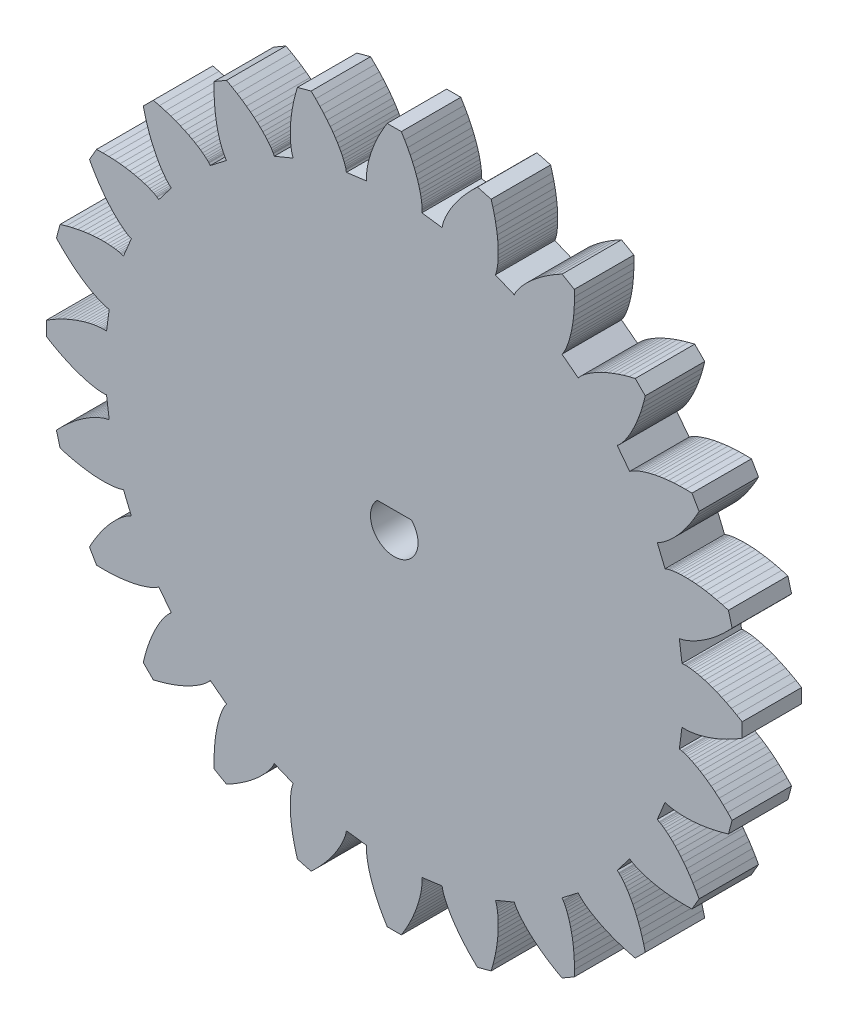
SolidWorks part; units mm, degrees
ref_plane "Front Plane" through (0, 0, 0) normal (0, 0, 1) x (1, 0, 0)
ref_plane "Top Plane" through (0, 0, 0) normal (0, 1, 0) x (1, 0, 0)
ref_plane "Right Plane" through (0, 0, 0) normal (1, 0, 0) x (0, 0, -1)
sketch "Model" plane through (0, 0, 0) normal (0, 0, 1) x (1, 0, 0)
  line L0 (24.1894, 2.3153) -> (24.359, 2.3315)
  line L1 (24.359, 2.3315) -> (24.3735, 2.3326)
  line L2 (24.3735, 2.3326) -> (24.417, 2.3344)
  line L3 (24.417, 2.3344) -> (24.4897, 2.335)
  line L4 (24.4897, 2.335) -> (24.5914, 2.3324)
  line L5 (24.5914, 2.3324) -> (24.7219, 2.3245)
  line L6 (24.7219, 2.3245) -> (24.8811, 2.3094)
  line L7 (24.8811, 2.3094) -> (25.0684, 2.2851)
  line L8 (25.0684, 2.2851) -> (25.2835, 2.2496)
  line L9 (25.2835, 2.2496) -> (25.5258, 2.201)
  line L10 (25.5258, 2.201) -> (25.7945, 2.1375)
  line L11 (25.7945, 2.1375) -> (26.0888, 2.057)
  line L12 (26.0888, 2.057) -> (26.4081, 1.9579)
  line L13 (26.4081, 1.9579) -> (26.7511, 1.8382)
  line L14 (26.7511, 1.8382) -> (27.1169, 1.6963)
  line L15 (27.1169, 1.6963) -> (27.5043, 1.5304)
  line L16 (27.5043, 1.5304) -> (27.9121, 1.339)
  line L17 (27.9121, 1.339) -> (28.339, 1.1203)
  line L18 (28.339, 1.1203) -> (28.7834, 0.8729)
  line L19 (28.7834, 0.8729) -> (29.244, 0.5954)
  line L20 (29.244, 0.5954) -> (29.244, -0.5954)
  line L21 (29.244, -0.5954) -> (28.7834, -0.8729)
  line L22 (28.7834, -0.8729) -> (28.339, -1.1203)
  line L23 (28.339, -1.1203) -> (27.9121, -1.339)
  line L24 (27.9121, -1.339) -> (27.5043, -1.5304)
  line L25 (27.5043, -1.5304) -> (27.1169, -1.6963)
  line L26 (27.1169, -1.6963) -> (26.7511, -1.8382)
  line L27 (26.7511, -1.8382) -> (26.4081, -1.9579)
  line L28 (26.4081, -1.9579) -> (26.0888, -2.057)
  line L29 (26.0888, -2.057) -> (25.7945, -2.1375)
  line L30 (25.7945, -2.1375) -> (25.5258, -2.201)
  line L31 (25.5258, -2.201) -> (25.2835, -2.2496)
  line L32 (25.2835, -2.2496) -> (25.0684, -2.2851)
  line L33 (25.0684, -2.2851) -> (24.8811, -2.3094)
  line L34 (24.8811, -2.3094) -> (24.7219, -2.3245)
  line L35 (24.7219, -2.3245) -> (24.5914, -2.3324)
  line L36 (24.5914, -2.3324) -> (24.4897, -2.335)
  line L37 (24.4897, -2.335) -> (24.417, -2.3344)
  line L38 (24.417, -2.3344) -> (24.3735, -2.3326)
  line L39 (24.3735, -2.3326) -> (24.359, -2.3315)
  line L40 (24.359, -2.3315) -> (24.1894, -2.3153)
  line L41 (24.1894, -2.3153) -> (23.9645, -4.0243)
  line L42 (23.9645, -4.0243) -> (24.1324, -4.0525)
  line L43 (24.1324, -4.0525) -> (24.1467, -4.0552)
  line L44 (24.1467, -4.0552) -> (24.1892, -4.0647)
  line L45 (24.1892, -4.0647) -> (24.2596, -4.083)
  line L46 (24.2596, -4.083) -> (24.3571, -4.1118)
  line L47 (24.3571, -4.1118) -> (24.4812, -4.1532)
  line L48 (24.4812, -4.1532) -> (24.631, -4.209)
  line L49 (24.631, -4.209) -> (24.8057, -4.281)
  line L50 (24.8057, -4.281) -> (25.0042, -4.3709)
  line L51 (25.0042, -4.3709) -> (25.2257, -4.4805)
  line L52 (25.2257, -4.4805) -> (25.4687, -4.6115)
  line L53 (25.4687, -4.6115) -> (25.7323, -4.7654)
  line L54 (25.7323, -4.7654) -> (26.015, -4.9437)
  line L55 (26.015, -4.9437) -> (26.3153, -5.1481)
  line L56 (26.3153, -5.1481) -> (26.632, -5.3799)
  line L57 (26.632, -5.3799) -> (26.9633, -5.6404)
  line L58 (26.9633, -5.6404) -> (27.3076, -5.9309)
  line L59 (27.3076, -5.9309) -> (27.6633, -6.2525)
  line L60 (27.6633, -6.2525) -> (28.0286, -6.6065)
  line L61 (28.0286, -6.6065) -> (28.4016, -6.9938)
  line L62 (28.4016, -6.9938) -> (28.0934, -8.144)
  line L63 (28.0934, -8.144) -> (27.5767, -8.2929)
  line L64 (27.5767, -8.2929) -> (27.0834, -8.4168)
  line L65 (27.0834, -8.4168) -> (26.6145, -8.5175)
  line L66 (26.6145, -8.5175) -> (26.1711, -8.5969)
  line L67 (26.1711, -8.5969) -> (25.7539, -8.6569)
  line L68 (25.7539, -8.6569) -> (25.3638, -8.6993)
  line L69 (25.3638, -8.6993) -> (25.0015, -8.7261)
  line L70 (25.0015, -8.7261) -> (24.6675, -8.7392)
  line L71 (24.6675, -8.7392) -> (24.3623, -8.7407)
  line L72 (24.3623, -8.7407) -> (24.0863, -8.7326)
  line L73 (24.0863, -8.7326) -> (23.8398, -8.7168)
  line L74 (23.8398, -8.7168) -> (23.6228, -8.6954)
  line L75 (23.6228, -8.6954) -> (23.4356, -8.6704)
  line L76 (23.4356, -8.6704) -> (23.2779, -8.6438)
  line L77 (23.2779, -8.6438) -> (23.1498, -8.6176)
  line L78 (23.1498, -8.6176) -> (23.0509, -8.5938)
  line L79 (23.0509, -8.5938) -> (22.9809, -8.5745)
  line L80 (22.9809, -8.5745) -> (22.9392, -8.5614)
  line L81 (22.9392, -8.5614) -> (22.9255, -8.5567)
  line L82 (22.9255, -8.5567) -> (22.766, -8.4971)
  line L83 (22.766, -8.4971) -> (22.1063, -10.0896)
  line L84 (22.1063, -10.0896) -> (22.2613, -10.1603)
  line L85 (22.2613, -10.1603) -> (22.2743, -10.1666)
  line L86 (22.2743, -10.1666) -> (22.313, -10.1868)
  line L87 (22.313, -10.1868) -> (22.3762, -10.2227)
  line L88 (22.3762, -10.2227) -> (22.463, -10.2758)
  line L89 (22.463, -10.2758) -> (22.5721, -10.3479)
  line L90 (22.5721, -10.3479) -> (22.7023, -10.4406)
  line L91 (22.7023, -10.4406) -> (22.8524, -10.5553)
  line L92 (22.8524, -10.5553) -> (23.021, -10.6936)
  line L93 (23.021, -10.6936) -> (23.2065, -10.8567)
  line L94 (23.2065, -10.8567) -> (23.4074, -11.0461)
  line L95 (23.4074, -11.0461) -> (23.6221, -11.263)
  line L96 (23.6221, -11.263) -> (23.849, -11.5085)
  line L97 (23.849, -11.5085) -> (24.0862, -11.7836)
  line L98 (24.0862, -11.7836) -> (24.3321, -12.0894)
  line L99 (24.3321, -12.0894) -> (24.5847, -12.4268)
  line L100 (24.5847, -12.4268) -> (24.8421, -12.7965)
  line L101 (24.8421, -12.7965) -> (25.1024, -13.1993)
  line L102 (25.1024, -13.1993) -> (25.3636, -13.6357)
  line L103 (25.3636, -13.6357) -> (25.6237, -14.1063)
  line L104 (25.6237, -14.1063) -> (25.0283, -15.1376)
  line L105 (25.0283, -15.1376) -> (24.4907, -15.1477)
  line L106 (24.4907, -15.1477) -> (23.9821, -15.1397)
  line L107 (23.9821, -15.1397) -> (23.5031, -15.1156)
  line L108 (23.5031, -15.1156) -> (23.0542, -15.0776)
  line L109 (23.0542, -15.0776) -> (22.6358, -15.0275)
  line L110 (22.6358, -15.0275) -> (22.248, -14.9675)
  line L111 (22.248, -14.9675) -> (21.8911, -14.8996)
  line L112 (21.8911, -14.8996) -> (21.5651, -14.8259)
  line L113 (21.5651, -14.8259) -> (21.2699, -14.7483)
  line L114 (21.2699, -14.7483) -> (21.0054, -14.669)
  line L115 (21.0054, -14.669) -> (20.7714, -14.59)
  line L116 (20.7714, -14.59) -> (20.5674, -14.5131)
  line L117 (20.5674, -14.5131) -> (20.393, -14.4405)
  line L118 (20.393, -14.4405) -> (20.2476, -14.374)
  line L119 (20.2476, -14.374) -> (20.1306, -14.3156)
  line L120 (20.1306, -14.3156) -> (20.0412, -14.267)
  line L121 (20.0412, -14.267) -> (19.9786, -14.2302)
  line L122 (19.9786, -14.2302) -> (19.9417, -14.2068)
  line L123 (19.9417, -14.2068) -> (19.9297, -14.1987)
  line L124 (19.9297, -14.1987) -> (19.791, -14.0998)
  line L125 (19.791, -14.0998) -> (18.7417, -15.4673)
  line L126 (18.7417, -15.4673) -> (18.8731, -15.5757)
  line L127 (18.8731, -15.5757) -> (18.884, -15.5853)
  line L128 (18.884, -15.5853) -> (18.9161, -15.6148)
  line L129 (18.9161, -15.6148) -> (18.9679, -15.6657)
  line L130 (18.9679, -15.6657) -> (19.038, -15.7395)
  line L131 (19.038, -15.7395) -> (19.1247, -15.8374)
  line L132 (19.1247, -15.8374) -> (19.2266, -15.9606)
  line L133 (19.2266, -15.9606) -> (19.3418, -16.1103)
  line L134 (19.3418, -16.1103) -> (19.4689, -16.2874)
  line L135 (19.4689, -16.2874) -> (19.6058, -16.4931)
  line L136 (19.6058, -16.4931) -> (19.7509, -16.728)
  line L137 (19.7509, -16.728) -> (19.9021, -16.9931)
  line L138 (19.9021, -16.9931) -> (20.0577, -17.2889)
  line L139 (20.0577, -17.2889) -> (20.2157, -17.6161)
  line L140 (20.2157, -17.6161) -> (20.374, -17.9751)
  line L141 (20.374, -17.9751) -> (20.5307, -18.3663)
  line L142 (20.5307, -18.3663) -> (20.6837, -18.7901)
  line L143 (20.6837, -18.7901) -> (20.8309, -19.2465)
  line L144 (20.8309, -19.2465) -> (20.9702, -19.7357)
  line L145 (20.9702, -19.7357) -> (21.0996, -20.2576)
  line L146 (21.0996, -20.2576) -> (20.2576, -21.0996)
  line L147 (20.2576, -21.0996) -> (19.7357, -20.9702)
  line L148 (19.7357, -20.9702) -> (19.2465, -20.8309)
  line L149 (19.2465, -20.8309) -> (18.7901, -20.6837)
  line L150 (18.7901, -20.6837) -> (18.3663, -20.5307)
  line L151 (18.3663, -20.5307) -> (17.9751, -20.374)
  line L152 (17.9751, -20.374) -> (17.6161, -20.2157)
  line L153 (17.6161, -20.2157) -> (17.2889, -20.0577)
  line L154 (17.2889, -20.0577) -> (16.9931, -19.9021)
  line L155 (16.9931, -19.9021) -> (16.728, -19.7509)
  line L156 (16.728, -19.7509) -> (16.4931, -19.6058)
  line L157 (16.4931, -19.6058) -> (16.2874, -19.4689)
  line L158 (16.2874, -19.4689) -> (16.1103, -19.3418)
  line L159 (16.1103, -19.3418) -> (15.9606, -19.2266)
  line L160 (15.9606, -19.2266) -> (15.8374, -19.1247)
  line L161 (15.8374, -19.1247) -> (15.7395, -19.038)
  line L162 (15.7395, -19.038) -> (15.6657, -18.9679)
  line L163 (15.6657, -18.9679) -> (15.6148, -18.9161)
  line L164 (15.6148, -18.9161) -> (15.5853, -18.884)
  line L165 (15.5853, -18.884) -> (15.5757, -18.8731)
  line L166 (15.5757, -18.8731) -> (15.4673, -18.7417)
  line L167 (15.4673, -18.7417) -> (14.0998, -19.791)
  line L168 (14.0998, -19.791) -> (14.1987, -19.9297)
  line L169 (14.1987, -19.9297) -> (14.2068, -19.9417)
  line L170 (14.2068, -19.9417) -> (14.2302, -19.9786)
  line L171 (14.2302, -19.9786) -> (14.267, -20.0412)
  line L172 (14.267, -20.0412) -> (14.3156, -20.1306)
  line L173 (14.3156, -20.1306) -> (14.374, -20.2476)
  line L174 (14.374, -20.2476) -> (14.4405, -20.393)
  line L175 (14.4405, -20.393) -> (14.5131, -20.5674)
  line L176 (14.5131, -20.5674) -> (14.59, -20.7714)
  line L177 (14.59, -20.7714) -> (14.669, -21.0054)
  line L178 (14.669, -21.0054) -> (14.7483, -21.2699)
  line L179 (14.7483, -21.2699) -> (14.8259, -21.5651)
  line L180 (14.8259, -21.5651) -> (14.8996, -21.8911)
  line L181 (14.8996, -21.8911) -> (14.9675, -22.248)
  line L182 (14.9675, -22.248) -> (15.0275, -22.6358)
  line L183 (15.0275, -22.6358) -> (15.0776, -23.0542)
  line L184 (15.0776, -23.0542) -> (15.1156, -23.5031)
  line L185 (15.1156, -23.5031) -> (15.1397, -23.9821)
  line L186 (15.1397, -23.9821) -> (15.1477, -24.4907)
  line L187 (15.1477, -24.4907) -> (15.1376, -25.0283)
  line L188 (15.1376, -25.0283) -> (14.1063, -25.6237)
  line L189 (14.1063, -25.6237) -> (13.6357, -25.3636)
  line L190 (13.6357, -25.3636) -> (13.1993, -25.1024)
  line L191 (13.1993, -25.1024) -> (12.7965, -24.8421)
  line L192 (12.7965, -24.8421) -> (12.4268, -24.5847)
  line L193 (12.4268, -24.5847) -> (12.0894, -24.3321)
  line L194 (12.0894, -24.3321) -> (11.7836, -24.0862)
  line L195 (11.7836, -24.0862) -> (11.5085, -23.849)
  line L196 (11.5085, -23.849) -> (11.263, -23.6221)
  line L197 (11.263, -23.6221) -> (11.0461, -23.4074)
  line L198 (11.0461, -23.4074) -> (10.8567, -23.2065)
  line L199 (10.8567, -23.2065) -> (10.6936, -23.021)
  line L200 (10.6936, -23.021) -> (10.5553, -22.8524)
  line L201 (10.5553, -22.8524) -> (10.4406, -22.7023)
  line L202 (10.4406, -22.7023) -> (10.3479, -22.5721)
  line L203 (10.3479, -22.5721) -> (10.2758, -22.463)
  line L204 (10.2758, -22.463) -> (10.2227, -22.3762)
  line L205 (10.2227, -22.3762) -> (10.1868, -22.313)
  line L206 (10.1868, -22.313) -> (10.1666, -22.2743)
  line L207 (10.1666, -22.2743) -> (10.1603, -22.2613)
  line L208 (10.1603, -22.2613) -> (10.0896, -22.1063)
  line L209 (10.0896, -22.1063) -> (8.4971, -22.766)
  line L210 (8.4971, -22.766) -> (8.5567, -22.9255)
  line L211 (8.5567, -22.9255) -> (8.5614, -22.9392)
  line L212 (8.5614, -22.9392) -> (8.5745, -22.9809)
  line L213 (8.5745, -22.9809) -> (8.5938, -23.0509)
  line L214 (8.5938, -23.0509) -> (8.6176, -23.1498)
  line L215 (8.6176, -23.1498) -> (8.6438, -23.2779)
  line L216 (8.6438, -23.2779) -> (8.6704, -23.4356)
  line L217 (8.6704, -23.4356) -> (8.6954, -23.6228)
  line L218 (8.6954, -23.6228) -> (8.7168, -23.8398)
  line L219 (8.7168, -23.8398) -> (8.7326, -24.0863)
  line L220 (8.7326, -24.0863) -> (8.7407, -24.3623)
  line L221 (8.7407, -24.3623) -> (8.7392, -24.6675)
  line L222 (8.7392, -24.6675) -> (8.7261, -25.0015)
  line L223 (8.7261, -25.0015) -> (8.6993, -25.3638)
  line L224 (8.6993, -25.3638) -> (8.6569, -25.7539)
  line L225 (8.6569, -25.7539) -> (8.5969, -26.1711)
  line L226 (8.5969, -26.1711) -> (8.5175, -26.6145)
  line L227 (8.5175, -26.6145) -> (8.4168, -27.0834)
  line L228 (8.4168, -27.0834) -> (8.2929, -27.5767)
  line L229 (8.2929, -27.5767) -> (8.144, -28.0934)
  line L230 (8.144, -28.0934) -> (6.9938, -28.4016)
  line L231 (6.9938, -28.4016) -> (6.6065, -28.0286)
  line L232 (6.6065, -28.0286) -> (6.2525, -27.6633)
  line L233 (6.2525, -27.6633) -> (5.9309, -27.3076)
  line L234 (5.9309, -27.3076) -> (5.6404, -26.9633)
  line L235 (5.6404, -26.9633) -> (5.3799, -26.632)
  line L236 (5.3799, -26.632) -> (5.1481, -26.3153)
  line L237 (5.1481, -26.3153) -> (4.9437, -26.015)
  line L238 (4.9437, -26.015) -> (4.7654, -25.7323)
  line L239 (4.7654, -25.7323) -> (4.6115, -25.4687)
  line L240 (4.6115, -25.4687) -> (4.4805, -25.2257)
  line L241 (4.4805, -25.2257) -> (4.3709, -25.0042)
  line L242 (4.3709, -25.0042) -> (4.281, -24.8057)
  line L243 (4.281, -24.8057) -> (4.209, -24.631)
  line L244 (4.209, -24.631) -> (4.1532, -24.4812)
  line L245 (4.1532, -24.4812) -> (4.1118, -24.3571)
  line L246 (4.1118, -24.3571) -> (4.083, -24.2596)
  line L247 (4.083, -24.2596) -> (4.0647, -24.1892)
  line L248 (4.0647, -24.1892) -> (4.0552, -24.1467)
  line L249 (4.0552, -24.1467) -> (4.0525, -24.1324)
  line L250 (4.0525, -24.1324) -> (4.0243, -23.9645)
  line L251 (4.0243, -23.9645) -> (2.3153, -24.1894)
  line L252 (2.3153, -24.1894) -> (2.3315, -24.359)
  line L253 (2.3315, -24.359) -> (2.3326, -24.3735)
  line L254 (2.3326, -24.3735) -> (2.3344, -24.417)
  line L255 (2.3344, -24.417) -> (2.335, -24.4897)
  line L256 (2.335, -24.4897) -> (2.3324, -24.5914)
  line L257 (2.3324, -24.5914) -> (2.3245, -24.7219)
  line L258 (2.3245, -24.7219) -> (2.3094, -24.8811)
  line L259 (2.3094, -24.8811) -> (2.2851, -25.0684)
  line L260 (2.2851, -25.0684) -> (2.2496, -25.2835)
  line L261 (2.2496, -25.2835) -> (2.201, -25.5258)
  line L262 (2.201, -25.5258) -> (2.1375, -25.7945)
  line L263 (2.1375, -25.7945) -> (2.057, -26.0888)
  line L264 (2.057, -26.0888) -> (1.9579, -26.4081)
  line L265 (1.9579, -26.4081) -> (1.8382, -26.7511)
  line L266 (1.8382, -26.7511) -> (1.6963, -27.1169)
  line L267 (1.6963, -27.1169) -> (1.5304, -27.5043)
  line L268 (1.5304, -27.5043) -> (1.339, -27.9121)
  line L269 (1.339, -27.9121) -> (1.1203, -28.339)
  line L270 (1.1203, -28.339) -> (0.8729, -28.7834)
  line L271 (0.8729, -28.7834) -> (0.5954, -29.244)
  line L272 (0.5954, -29.244) -> (-0.5954, -29.244)
  line L273 (-0.5954, -29.244) -> (-0.8729, -28.7834)
  line L274 (-0.8729, -28.7834) -> (-1.1203, -28.339)
  line L275 (-1.1203, -28.339) -> (-1.339, -27.9121)
  line L276 (-1.339, -27.9121) -> (-1.5304, -27.5043)
  line L277 (-1.5304, -27.5043) -> (-1.6963, -27.1169)
  line L278 (-1.6963, -27.1169) -> (-1.8382, -26.7511)
  line L279 (-1.8382, -26.7511) -> (-1.9579, -26.4081)
  line L280 (-1.9579, -26.4081) -> (-2.057, -26.0888)
  line L281 (-2.057, -26.0888) -> (-2.1375, -25.7945)
  line L282 (-2.1375, -25.7945) -> (-2.201, -25.5258)
  line L283 (-2.201, -25.5258) -> (-2.2496, -25.2835)
  line L284 (-2.2496, -25.2835) -> (-2.2851, -25.0684)
  line L285 (-2.2851, -25.0684) -> (-2.3094, -24.8811)
  line L286 (-2.3094, -24.8811) -> (-2.3245, -24.7219)
  line L287 (-2.3245, -24.7219) -> (-2.3324, -24.5914)
  line L288 (-2.3324, -24.5914) -> (-2.335, -24.4897)
  line L289 (-2.335, -24.4897) -> (-2.3344, -24.417)
  line L290 (-2.3344, -24.417) -> (-2.3326, -24.3735)
  line L291 (-2.3326, -24.3735) -> (-2.3315, -24.359)
  line L292 (-2.3315, -24.359) -> (-2.3153, -24.1894)
  line L293 (-2.3153, -24.1894) -> (-4.0243, -23.9645)
  line L294 (-4.0243, -23.9645) -> (-4.0525, -24.1324)
  line L295 (-4.0525, -24.1324) -> (-4.0552, -24.1467)
  line L296 (-4.0552, -24.1467) -> (-4.0647, -24.1892)
  line L297 (-4.0647, -24.1892) -> (-4.083, -24.2596)
  line L298 (-4.083, -24.2596) -> (-4.1118, -24.3571)
  line L299 (-4.1118, -24.3571) -> (-4.1532, -24.4812)
  line L300 (-4.1532, -24.4812) -> (-4.209, -24.631)
  line L301 (-4.209, -24.631) -> (-4.281, -24.8057)
  line L302 (-4.281, -24.8057) -> (-4.3709, -25.0042)
  line L303 (-4.3709, -25.0042) -> (-4.4805, -25.2257)
  line L304 (-4.4805, -25.2257) -> (-4.6115, -25.4687)
  line L305 (-4.6115, -25.4687) -> (-4.7654, -25.7323)
  line L306 (-4.7654, -25.7323) -> (-4.9437, -26.015)
  line L307 (-4.9437, -26.015) -> (-5.1481, -26.3153)
  line L308 (-5.1481, -26.3153) -> (-5.3799, -26.632)
  line L309 (-5.3799, -26.632) -> (-5.6404, -26.9633)
  line L310 (-5.6404, -26.9633) -> (-5.9309, -27.3076)
  line L311 (-5.9309, -27.3076) -> (-6.2525, -27.6633)
  line L312 (-6.2525, -27.6633) -> (-6.6065, -28.0286)
  line L313 (-6.6065, -28.0286) -> (-6.9938, -28.4016)
  line L314 (-6.9938, -28.4016) -> (-8.144, -28.0934)
  line L315 (-8.144, -28.0934) -> (-8.2929, -27.5767)
  line L316 (-8.2929, -27.5767) -> (-8.4168, -27.0834)
  line L317 (-8.4168, -27.0834) -> (-8.5175, -26.6145)
  line L318 (-8.5175, -26.6145) -> (-8.5969, -26.1711)
  line L319 (-8.5969, -26.1711) -> (-8.6569, -25.7539)
  line L320 (-8.6569, -25.7539) -> (-8.6993, -25.3638)
  line L321 (-8.6993, -25.3638) -> (-8.7261, -25.0015)
  line L322 (-8.7261, -25.0015) -> (-8.7392, -24.6675)
  line L323 (-8.7392, -24.6675) -> (-8.7407, -24.3623)
  line L324 (-8.7407, -24.3623) -> (-8.7326, -24.0863)
  line L325 (-8.7326, -24.0863) -> (-8.7168, -23.8398)
  line L326 (-8.7168, -23.8398) -> (-8.6954, -23.6228)
  line L327 (-8.6954, -23.6228) -> (-8.6704, -23.4356)
  line L328 (-8.6704, -23.4356) -> (-8.6438, -23.2779)
  line L329 (-8.6438, -23.2779) -> (-8.6176, -23.1498)
  line L330 (-8.6176, -23.1498) -> (-8.5938, -23.0509)
  line L331 (-8.5938, -23.0509) -> (-8.5745, -22.9809)
  line L332 (-8.5745, -22.9809) -> (-8.5614, -22.9392)
  line L333 (-8.5614, -22.9392) -> (-8.5567, -22.9255)
  line L334 (-8.5567, -22.9255) -> (-8.4971, -22.766)
  line L335 (-8.4971, -22.766) -> (-10.0896, -22.1063)
  line L336 (-10.0896, -22.1063) -> (-10.1603, -22.2613)
  line L337 (-10.1603, -22.2613) -> (-10.1666, -22.2743)
  line L338 (-10.1666, -22.2743) -> (-10.1868, -22.313)
  line L339 (-10.1868, -22.313) -> (-10.2227, -22.3762)
  line L340 (-10.2227, -22.3762) -> (-10.2758, -22.463)
  line L341 (-10.2758, -22.463) -> (-10.3479, -22.5721)
  line L342 (-10.3479, -22.5721) -> (-10.4406, -22.7023)
  line L343 (-10.4406, -22.7023) -> (-10.5553, -22.8524)
  line L344 (-10.5553, -22.8524) -> (-10.6936, -23.021)
  line L345 (-10.6936, -23.021) -> (-10.8567, -23.2065)
  line L346 (-10.8567, -23.2065) -> (-11.0461, -23.4074)
  line L347 (-11.0461, -23.4074) -> (-11.263, -23.6221)
  line L348 (-11.263, -23.6221) -> (-11.5085, -23.849)
  line L349 (-11.5085, -23.849) -> (-11.7836, -24.0862)
  line L350 (-11.7836, -24.0862) -> (-12.0894, -24.3321)
  line L351 (-12.0894, -24.3321) -> (-12.4268, -24.5847)
  line L352 (-12.4268, -24.5847) -> (-12.7965, -24.8421)
  line L353 (-12.7965, -24.8421) -> (-13.1993, -25.1024)
  line L354 (-13.1993, -25.1024) -> (-13.6357, -25.3636)
  line L355 (-13.6357, -25.3636) -> (-14.1063, -25.6237)
  line L356 (-14.1063, -25.6237) -> (-15.1376, -25.0283)
  line L357 (-15.1376, -25.0283) -> (-15.1477, -24.4907)
  line L358 (-15.1477, -24.4907) -> (-15.1397, -23.9821)
  line L359 (-15.1397, -23.9821) -> (-15.1156, -23.5031)
  line L360 (-15.1156, -23.5031) -> (-15.0776, -23.0542)
  line L361 (-15.0776, -23.0542) -> (-15.0275, -22.6358)
  line L362 (-15.0275, -22.6358) -> (-14.9675, -22.248)
  line L363 (-14.9675, -22.248) -> (-14.8996, -21.8911)
  line L364 (-14.8996, -21.8911) -> (-14.8259, -21.5651)
  line L365 (-14.8259, -21.5651) -> (-14.7483, -21.2699)
  line L366 (-14.7483, -21.2699) -> (-14.669, -21.0054)
  line L367 (-14.669, -21.0054) -> (-14.59, -20.7714)
  line L368 (-14.59, -20.7714) -> (-14.5131, -20.5674)
  line L369 (-14.5131, -20.5674) -> (-14.4405, -20.393)
  line L370 (-14.4405, -20.393) -> (-14.374, -20.2476)
  line L371 (-14.374, -20.2476) -> (-14.3156, -20.1306)
  line L372 (-14.3156, -20.1306) -> (-14.267, -20.0412)
  line L373 (-14.267, -20.0412) -> (-14.2302, -19.9786)
  line L374 (-14.2302, -19.9786) -> (-14.2068, -19.9417)
  line L375 (-14.2068, -19.9417) -> (-14.1987, -19.9297)
  line L376 (-14.1987, -19.9297) -> (-14.0998, -19.791)
  line L377 (-14.0998, -19.791) -> (-15.4673, -18.7417)
  line L378 (-15.4673, -18.7417) -> (-15.5757, -18.8731)
  line L379 (-15.5757, -18.8731) -> (-15.5853, -18.884)
  line L380 (-15.5853, -18.884) -> (-15.6148, -18.9161)
  line L381 (-15.6148, -18.9161) -> (-15.6657, -18.9679)
  line L382 (-15.6657, -18.9679) -> (-15.7395, -19.038)
  line L383 (-15.7395, -19.038) -> (-15.8374, -19.1247)
  line L384 (-15.8374, -19.1247) -> (-15.9606, -19.2266)
  line L385 (-15.9606, -19.2266) -> (-16.1103, -19.3418)
  line L386 (-16.1103, -19.3418) -> (-16.2874, -19.4689)
  line L387 (-16.2874, -19.4689) -> (-16.4931, -19.6058)
  line L388 (-16.4931, -19.6058) -> (-16.728, -19.7509)
  line L389 (-16.728, -19.7509) -> (-16.9931, -19.9021)
  line L390 (-16.9931, -19.9021) -> (-17.2889, -20.0577)
  line L391 (-17.2889, -20.0577) -> (-17.6161, -20.2157)
  line L392 (-17.6161, -20.2157) -> (-17.9751, -20.374)
  line L393 (-17.9751, -20.374) -> (-18.3663, -20.5307)
  line L394 (-18.3663, -20.5307) -> (-18.7901, -20.6837)
  line L395 (-18.7901, -20.6837) -> (-19.2465, -20.8309)
  line L396 (-19.2465, -20.8309) -> (-19.7357, -20.9702)
  line L397 (-19.7357, -20.9702) -> (-20.2576, -21.0996)
  line L398 (-20.2576, -21.0996) -> (-21.0996, -20.2576)
  line L399 (-21.0996, -20.2576) -> (-20.9702, -19.7357)
  line L400 (-20.9702, -19.7357) -> (-20.8309, -19.2465)
  line L401 (-20.8309, -19.2465) -> (-20.6837, -18.7901)
  line L402 (-20.6837, -18.7901) -> (-20.5307, -18.3663)
  line L403 (-20.5307, -18.3663) -> (-20.374, -17.9751)
  line L404 (-20.374, -17.9751) -> (-20.2157, -17.6161)
  line L405 (-20.2157, -17.6161) -> (-20.0577, -17.2889)
  line L406 (-20.0577, -17.2889) -> (-19.9021, -16.9931)
  line L407 (-19.9021, -16.9931) -> (-19.7509, -16.728)
  line L408 (-19.7509, -16.728) -> (-19.6058, -16.4931)
  line L409 (-19.6058, -16.4931) -> (-19.4689, -16.2874)
  line L410 (-19.4689, -16.2874) -> (-19.3418, -16.1103)
  line L411 (-19.3418, -16.1103) -> (-19.2266, -15.9606)
  line L412 (-19.2266, -15.9606) -> (-19.1247, -15.8374)
  line L413 (-19.1247, -15.8374) -> (-19.038, -15.7395)
  line L414 (-19.038, -15.7395) -> (-18.9679, -15.6657)
  line L415 (-18.9679, -15.6657) -> (-18.9161, -15.6148)
  line L416 (-18.9161, -15.6148) -> (-18.884, -15.5853)
  line L417 (-18.884, -15.5853) -> (-18.8731, -15.5757)
  line L418 (-18.8731, -15.5757) -> (-18.7417, -15.4673)
  line L419 (-18.7417, -15.4673) -> (-19.791, -14.0998)
  line L420 (-19.791, -14.0998) -> (-19.9297, -14.1987)
  line L421 (-19.9297, -14.1987) -> (-19.9417, -14.2068)
  line L422 (-19.9417, -14.2068) -> (-19.9786, -14.2302)
  line L423 (-19.9786, -14.2302) -> (-20.0412, -14.267)
  line L424 (-20.0412, -14.267) -> (-20.1306, -14.3156)
  line L425 (-20.1306, -14.3156) -> (-20.2476, -14.374)
  line L426 (-20.2476, -14.374) -> (-20.393, -14.4405)
  line L427 (-20.393, -14.4405) -> (-20.5674, -14.5131)
  line L428 (-20.5674, -14.5131) -> (-20.7714, -14.59)
  line L429 (-20.7714, -14.59) -> (-21.0054, -14.669)
  line L430 (-21.0054, -14.669) -> (-21.2699, -14.7483)
  line L431 (-21.2699, -14.7483) -> (-21.5651, -14.8259)
  line L432 (-21.5651, -14.8259) -> (-21.8911, -14.8996)
  line L433 (-21.8911, -14.8996) -> (-22.248, -14.9675)
  line L434 (-22.248, -14.9675) -> (-22.6358, -15.0275)
  line L435 (-22.6358, -15.0275) -> (-23.0542, -15.0776)
  line L436 (-23.0542, -15.0776) -> (-23.5031, -15.1156)
  line L437 (-23.5031, -15.1156) -> (-23.9821, -15.1397)
  line L438 (-23.9821, -15.1397) -> (-24.4907, -15.1477)
  line L439 (-24.4907, -15.1477) -> (-25.0283, -15.1376)
  line L440 (-25.0283, -15.1376) -> (-25.6237, -14.1063)
  line L441 (-25.6237, -14.1063) -> (-25.3636, -13.6357)
  line L442 (-25.3636, -13.6357) -> (-25.1024, -13.1993)
  line L443 (-25.1024, -13.1993) -> (-24.8421, -12.7965)
  line L444 (-24.8421, -12.7965) -> (-24.5847, -12.4268)
  line L445 (-24.5847, -12.4268) -> (-24.3321, -12.0894)
  line L446 (-24.3321, -12.0894) -> (-24.0862, -11.7836)
  line L447 (-24.0862, -11.7836) -> (-23.849, -11.5085)
  line L448 (-23.849, -11.5085) -> (-23.6221, -11.263)
  line L449 (-23.6221, -11.263) -> (-23.4074, -11.0461)
  line L450 (-23.4074, -11.0461) -> (-23.2065, -10.8567)
  line L451 (-23.2065, -10.8567) -> (-23.021, -10.6936)
  line L452 (-23.021, -10.6936) -> (-22.8524, -10.5553)
  line L453 (-22.8524, -10.5553) -> (-22.7023, -10.4406)
  line L454 (-22.7023, -10.4406) -> (-22.5721, -10.3479)
  line L455 (-22.5721, -10.3479) -> (-22.463, -10.2758)
  line L456 (-22.463, -10.2758) -> (-22.3762, -10.2227)
  line L457 (-22.3762, -10.2227) -> (-22.313, -10.1868)
  line L458 (-22.313, -10.1868) -> (-22.2743, -10.1666)
  line L459 (-22.2743, -10.1666) -> (-22.2613, -10.1603)
  line L460 (-22.2613, -10.1603) -> (-22.1063, -10.0896)
  line L461 (-22.1063, -10.0896) -> (-22.766, -8.4971)
  line L462 (-22.766, -8.4971) -> (-22.9255, -8.5567)
  line L463 (-22.9255, -8.5567) -> (-22.9392, -8.5614)
  line L464 (-22.9392, -8.5614) -> (-22.9809, -8.5745)
  line L465 (-22.9809, -8.5745) -> (-23.0509, -8.5938)
  line L466 (-23.0509, -8.5938) -> (-23.1498, -8.6176)
  line L467 (-23.1498, -8.6176) -> (-23.2779, -8.6438)
  line L468 (-23.2779, -8.6438) -> (-23.4356, -8.6704)
  line L469 (-23.4356, -8.6704) -> (-23.6228, -8.6954)
  line L470 (-23.6228, -8.6954) -> (-23.8398, -8.7168)
  line L471 (-23.8398, -8.7168) -> (-24.0863, -8.7326)
  line L472 (-24.0863, -8.7326) -> (-24.3623, -8.7407)
  line L473 (-24.3623, -8.7407) -> (-24.6675, -8.7392)
  line L474 (-24.6675, -8.7392) -> (-25.0015, -8.7261)
  line L475 (-25.0015, -8.7261) -> (-25.3638, -8.6993)
  line L476 (-25.3638, -8.6993) -> (-25.7539, -8.6569)
  line L477 (-25.7539, -8.6569) -> (-26.1711, -8.5969)
  line L478 (-26.1711, -8.5969) -> (-26.6145, -8.5175)
  line L479 (-26.6145, -8.5175) -> (-27.0834, -8.4168)
  line L480 (-27.0834, -8.4168) -> (-27.5767, -8.2929)
  line L481 (-27.5767, -8.2929) -> (-28.0934, -8.144)
  line L482 (-28.0934, -8.144) -> (-28.4016, -6.9938)
  line L483 (-28.4016, -6.9938) -> (-28.0286, -6.6065)
  line L484 (-28.0286, -6.6065) -> (-27.6633, -6.2525)
  line L485 (-27.6633, -6.2525) -> (-27.3076, -5.9309)
  line L486 (-27.3076, -5.9309) -> (-26.9633, -5.6404)
  line L487 (-26.9633, -5.6404) -> (-26.632, -5.3799)
  line L488 (-26.632, -5.3799) -> (-26.3153, -5.1481)
  line L489 (-26.3153, -5.1481) -> (-26.015, -4.9437)
  line L490 (-26.015, -4.9437) -> (-25.7323, -4.7654)
  line L491 (-25.7323, -4.7654) -> (-25.4687, -4.6115)
  line L492 (-25.4687, -4.6115) -> (-25.2257, -4.4805)
  line L493 (-25.2257, -4.4805) -> (-25.0042, -4.3709)
  line L494 (-25.0042, -4.3709) -> (-24.8057, -4.281)
  line L495 (-24.8057, -4.281) -> (-24.631, -4.209)
  line L496 (-24.631, -4.209) -> (-24.4812, -4.1532)
  line L497 (-24.4812, -4.1532) -> (-24.3571, -4.1118)
  line L498 (-24.3571, -4.1118) -> (-24.2596, -4.083)
  line L499 (-24.2596, -4.083) -> (-24.1892, -4.0647)
  line L500 (-24.1892, -4.0647) -> (-24.1467, -4.0552)
  line L501 (-24.1467, -4.0552) -> (-24.1324, -4.0525)
  line L502 (-24.1324, -4.0525) -> (-23.9645, -4.0243)
  line L503 (-23.9645, -4.0243) -> (-24.1894, -2.3153)
  line L504 (-24.1894, -2.3153) -> (-24.359, -2.3315)
  line L505 (-24.359, -2.3315) -> (-24.3735, -2.3326)
  line L506 (-24.3735, -2.3326) -> (-24.417, -2.3344)
  line L507 (-24.417, -2.3344) -> (-24.4897, -2.335)
  line L508 (-24.4897, -2.335) -> (-24.5914, -2.3324)
  line L509 (-24.5914, -2.3324) -> (-24.7219, -2.3245)
  line L510 (-24.7219, -2.3245) -> (-24.8811, -2.3094)
  line L511 (-24.8811, -2.3094) -> (-25.0684, -2.2851)
  line L512 (-25.0684, -2.2851) -> (-25.2835, -2.2496)
  line L513 (-25.2835, -2.2496) -> (-25.5258, -2.201)
  line L514 (-25.5258, -2.201) -> (-25.7945, -2.1375)
  line L515 (-25.7945, -2.1375) -> (-26.0888, -2.057)
  line L516 (-26.0888, -2.057) -> (-26.4081, -1.9579)
  line L517 (-26.4081, -1.9579) -> (-26.7511, -1.8382)
  line L518 (-26.7511, -1.8382) -> (-27.1169, -1.6963)
  line L519 (-27.1169, -1.6963) -> (-27.5043, -1.5304)
  line L520 (-27.5043, -1.5304) -> (-27.9121, -1.339)
  line L521 (-27.9121, -1.339) -> (-28.339, -1.1203)
  line L522 (-28.339, -1.1203) -> (-28.7834, -0.8729)
  line L523 (-28.7834, -0.8729) -> (-29.244, -0.5954)
  line L524 (-29.244, -0.5954) -> (-29.244, 0.5954)
  line L525 (-29.244, 0.5954) -> (-28.7834, 0.8729)
  line L526 (-28.7834, 0.8729) -> (-28.339, 1.1203)
  line L527 (-28.339, 1.1203) -> (-27.9121, 1.339)
  line L528 (-27.9121, 1.339) -> (-27.5043, 1.5304)
  line L529 (-27.5043, 1.5304) -> (-27.1169, 1.6963)
  line L530 (-27.1169, 1.6963) -> (-26.7511, 1.8382)
  line L531 (-26.7511, 1.8382) -> (-26.4081, 1.9579)
  line L532 (-26.4081, 1.9579) -> (-26.0888, 2.057)
  line L533 (-26.0888, 2.057) -> (-25.7945, 2.1375)
  line L534 (-25.7945, 2.1375) -> (-25.5258, 2.201)
  line L535 (-25.5258, 2.201) -> (-25.2835, 2.2496)
  line L536 (-25.2835, 2.2496) -> (-25.0684, 2.2851)
  line L537 (-25.0684, 2.2851) -> (-24.8811, 2.3094)
  line L538 (-24.8811, 2.3094) -> (-24.7219, 2.3245)
  line L539 (-24.7219, 2.3245) -> (-24.5914, 2.3324)
  line L540 (-24.5914, 2.3324) -> (-24.4897, 2.335)
  line L541 (-24.4897, 2.335) -> (-24.417, 2.3344)
  line L542 (-24.417, 2.3344) -> (-24.3735, 2.3326)
  line L543 (-24.3735, 2.3326) -> (-24.359, 2.3315)
  line L544 (-24.359, 2.3315) -> (-24.1894, 2.3153)
  line L545 (-24.1894, 2.3153) -> (-23.9645, 4.0243)
  line L546 (-23.9645, 4.0243) -> (-24.1324, 4.0525)
  line L547 (-24.1324, 4.0525) -> (-24.1467, 4.0552)
  line L548 (-24.1467, 4.0552) -> (-24.1892, 4.0647)
  line L549 (-24.1892, 4.0647) -> (-24.2596, 4.083)
  line L550 (-24.2596, 4.083) -> (-24.3571, 4.1118)
  line L551 (-24.3571, 4.1118) -> (-24.4812, 4.1532)
  line L552 (-24.4812, 4.1532) -> (-24.631, 4.209)
  line L553 (-24.631, 4.209) -> (-24.8057, 4.281)
  line L554 (-24.8057, 4.281) -> (-25.0042, 4.3709)
  line L555 (-25.0042, 4.3709) -> (-25.2257, 4.4805)
  line L556 (-25.2257, 4.4805) -> (-25.4687, 4.6115)
  line L557 (-25.4687, 4.6115) -> (-25.7323, 4.7654)
  line L558 (-25.7323, 4.7654) -> (-26.015, 4.9437)
  line L559 (-26.015, 4.9437) -> (-26.3153, 5.1481)
  line L560 (-26.3153, 5.1481) -> (-26.632, 5.3799)
  line L561 (-26.632, 5.3799) -> (-26.9633, 5.6404)
  line L562 (-26.9633, 5.6404) -> (-27.3076, 5.9309)
  line L563 (-27.3076, 5.9309) -> (-27.6633, 6.2525)
  line L564 (-27.6633, 6.2525) -> (-28.0286, 6.6065)
  line L565 (-28.0286, 6.6065) -> (-28.4016, 6.9938)
  line L566 (-28.4016, 6.9938) -> (-28.0934, 8.144)
  line L567 (-28.0934, 8.144) -> (-27.5767, 8.2929)
  line L568 (-27.5767, 8.2929) -> (-27.0834, 8.4168)
  line L569 (-27.0834, 8.4168) -> (-26.6145, 8.5175)
  line L570 (-26.6145, 8.5175) -> (-26.1711, 8.5969)
  line L571 (-26.1711, 8.5969) -> (-25.7539, 8.6569)
  line L572 (-25.7539, 8.6569) -> (-25.3638, 8.6993)
  line L573 (-25.3638, 8.6993) -> (-25.0015, 8.7261)
  line L574 (-25.0015, 8.7261) -> (-24.6675, 8.7392)
  line L575 (-24.6675, 8.7392) -> (-24.3623, 8.7407)
  line L576 (-24.3623, 8.7407) -> (-24.0863, 8.7326)
  line L577 (-24.0863, 8.7326) -> (-23.8398, 8.7168)
  line L578 (-23.8398, 8.7168) -> (-23.6228, 8.6954)
  line L579 (-23.6228, 8.6954) -> (-23.4356, 8.6704)
  line L580 (-23.4356, 8.6704) -> (-23.2779, 8.6438)
  line L581 (-23.2779, 8.6438) -> (-23.1498, 8.6176)
  line L582 (-23.1498, 8.6176) -> (-23.0509, 8.5938)
  line L583 (-23.0509, 8.5938) -> (-22.9809, 8.5745)
  line L584 (-22.9809, 8.5745) -> (-22.9392, 8.5614)
  line L585 (-22.9392, 8.5614) -> (-22.9255, 8.5567)
  line L586 (-22.9255, 8.5567) -> (-22.766, 8.4971)
  line L587 (-22.766, 8.4971) -> (-22.1063, 10.0896)
  line L588 (-22.1063, 10.0896) -> (-22.2613, 10.1603)
  line L589 (-22.2613, 10.1603) -> (-22.2743, 10.1666)
  line L590 (-22.2743, 10.1666) -> (-22.313, 10.1868)
  line L591 (-22.313, 10.1868) -> (-22.3762, 10.2227)
  line L592 (-22.3762, 10.2227) -> (-22.463, 10.2758)
  line L593 (-22.463, 10.2758) -> (-22.5721, 10.3479)
  line L594 (-22.5721, 10.3479) -> (-22.7023, 10.4406)
  line L595 (-22.7023, 10.4406) -> (-22.8524, 10.5553)
  line L596 (-22.8524, 10.5553) -> (-23.021, 10.6936)
  line L597 (-23.021, 10.6936) -> (-23.2065, 10.8567)
  line L598 (-23.2065, 10.8567) -> (-23.4074, 11.0461)
  line L599 (-23.4074, 11.0461) -> (-23.6221, 11.263)
  line L600 (-23.6221, 11.263) -> (-23.849, 11.5085)
  line L601 (-23.849, 11.5085) -> (-24.0862, 11.7836)
  line L602 (-24.0862, 11.7836) -> (-24.3321, 12.0894)
  line L603 (-24.3321, 12.0894) -> (-24.5847, 12.4268)
  line L604 (-24.5847, 12.4268) -> (-24.8421, 12.7965)
  line L605 (-24.8421, 12.7965) -> (-25.1024, 13.1993)
  line L606 (-25.1024, 13.1993) -> (-25.3636, 13.6357)
  line L607 (-25.3636, 13.6357) -> (-25.6237, 14.1063)
  line L608 (-25.6237, 14.1063) -> (-25.0283, 15.1376)
  line L609 (-25.0283, 15.1376) -> (-24.4907, 15.1477)
  line L610 (-24.4907, 15.1477) -> (-23.9821, 15.1397)
  line L611 (-23.9821, 15.1397) -> (-23.5031, 15.1156)
  line L612 (-23.5031, 15.1156) -> (-23.0542, 15.0776)
  line L613 (-23.0542, 15.0776) -> (-22.6358, 15.0275)
  line L614 (-22.6358, 15.0275) -> (-22.248, 14.9675)
  line L615 (-22.248, 14.9675) -> (-21.8911, 14.8996)
  line L616 (-21.8911, 14.8996) -> (-21.5651, 14.8259)
  line L617 (-21.5651, 14.8259) -> (-21.2699, 14.7483)
  line L618 (-21.2699, 14.7483) -> (-21.0054, 14.669)
  line L619 (-21.0054, 14.669) -> (-20.7714, 14.59)
  line L620 (-20.7714, 14.59) -> (-20.5674, 14.5131)
  line L621 (-20.5674, 14.5131) -> (-20.393, 14.4405)
  line L622 (-20.393, 14.4405) -> (-20.2476, 14.374)
  line L623 (-20.2476, 14.374) -> (-20.1306, 14.3156)
  line L624 (-20.1306, 14.3156) -> (-20.0412, 14.267)
  line L625 (-20.0412, 14.267) -> (-19.9786, 14.2302)
  line L626 (-19.9786, 14.2302) -> (-19.9417, 14.2068)
  line L627 (-19.9417, 14.2068) -> (-19.9297, 14.1987)
  line L628 (-19.9297, 14.1987) -> (-19.791, 14.0998)
  line L629 (-19.791, 14.0998) -> (-18.7417, 15.4673)
  line L630 (-18.7417, 15.4673) -> (-18.8731, 15.5757)
  line L631 (-18.8731, 15.5757) -> (-18.884, 15.5853)
  line L632 (-18.884, 15.5853) -> (-18.9161, 15.6148)
  line L633 (-18.9161, 15.6148) -> (-18.9679, 15.6657)
  line L634 (-18.9679, 15.6657) -> (-19.038, 15.7395)
  line L635 (-19.038, 15.7395) -> (-19.1247, 15.8374)
  line L636 (-19.1247, 15.8374) -> (-19.2266, 15.9606)
  line L637 (-19.2266, 15.9606) -> (-19.3418, 16.1103)
  line L638 (-19.3418, 16.1103) -> (-19.4689, 16.2874)
  line L639 (-19.4689, 16.2874) -> (-19.6058, 16.4931)
  line L640 (-19.6058, 16.4931) -> (-19.7509, 16.728)
  line L641 (-19.7509, 16.728) -> (-19.9021, 16.9931)
  line L642 (-19.9021, 16.9931) -> (-20.0577, 17.2889)
  line L643 (-20.0577, 17.2889) -> (-20.2157, 17.6161)
  line L644 (-20.2157, 17.6161) -> (-20.374, 17.9751)
  line L645 (-20.374, 17.9751) -> (-20.5307, 18.3663)
  line L646 (-20.5307, 18.3663) -> (-20.6837, 18.7901)
  line L647 (-20.6837, 18.7901) -> (-20.8309, 19.2465)
  line L648 (-20.8309, 19.2465) -> (-20.9702, 19.7357)
  line L649 (-20.9702, 19.7357) -> (-21.0996, 20.2576)
  line L650 (-21.0996, 20.2576) -> (-20.2576, 21.0996)
  line L651 (-20.2576, 21.0996) -> (-19.7357, 20.9702)
  line L652 (-19.7357, 20.9702) -> (-19.2465, 20.8309)
  line L653 (-19.2465, 20.8309) -> (-18.7901, 20.6837)
  line L654 (-18.7901, 20.6837) -> (-18.3663, 20.5307)
  line L655 (-18.3663, 20.5307) -> (-17.9751, 20.374)
  line L656 (-17.9751, 20.374) -> (-17.6161, 20.2157)
  line L657 (-17.6161, 20.2157) -> (-17.2889, 20.0577)
  line L658 (-17.2889, 20.0577) -> (-16.9931, 19.9021)
  line L659 (-16.9931, 19.9021) -> (-16.728, 19.7509)
  line L660 (-16.728, 19.7509) -> (-16.4931, 19.6058)
  line L661 (-16.4931, 19.6058) -> (-16.2874, 19.4689)
  line L662 (-16.2874, 19.4689) -> (-16.1103, 19.3418)
  line L663 (-16.1103, 19.3418) -> (-15.9606, 19.2266)
  line L664 (-15.9606, 19.2266) -> (-15.8374, 19.1247)
  line L665 (-15.8374, 19.1247) -> (-15.7395, 19.038)
  line L666 (-15.7395, 19.038) -> (-15.6657, 18.9679)
  line L667 (-15.6657, 18.9679) -> (-15.6148, 18.9161)
  line L668 (-15.6148, 18.9161) -> (-15.5853, 18.884)
  line L669 (-15.5853, 18.884) -> (-15.5757, 18.8731)
  line L670 (-15.5757, 18.8731) -> (-15.4673, 18.7417)
  line L671 (-15.4673, 18.7417) -> (-14.0998, 19.791)
  line L672 (-14.0998, 19.791) -> (-14.1987, 19.9297)
  line L673 (-14.1987, 19.9297) -> (-14.2068, 19.9417)
  line L674 (-14.2068, 19.9417) -> (-14.2302, 19.9786)
  line L675 (-14.2302, 19.9786) -> (-14.267, 20.0412)
  line L676 (-14.267, 20.0412) -> (-14.3156, 20.1306)
  line L677 (-14.3156, 20.1306) -> (-14.374, 20.2476)
  line L678 (-14.374, 20.2476) -> (-14.4405, 20.393)
  line L679 (-14.4405, 20.393) -> (-14.5131, 20.5674)
  line L680 (-14.5131, 20.5674) -> (-14.59, 20.7714)
  line L681 (-14.59, 20.7714) -> (-14.669, 21.0054)
  line L682 (-14.669, 21.0054) -> (-14.7483, 21.2699)
  line L683 (-14.7483, 21.2699) -> (-14.8259, 21.5651)
  line L684 (-14.8259, 21.5651) -> (-14.8996, 21.8911)
  line L685 (-14.8996, 21.8911) -> (-14.9675, 22.248)
  line L686 (-14.9675, 22.248) -> (-15.0275, 22.6358)
  line L687 (-15.0275, 22.6358) -> (-15.0776, 23.0542)
  line L688 (-15.0776, 23.0542) -> (-15.1156, 23.5031)
  line L689 (-15.1156, 23.5031) -> (-15.1397, 23.9821)
  line L690 (-15.1397, 23.9821) -> (-15.1477, 24.4907)
  line L691 (-15.1477, 24.4907) -> (-15.1376, 25.0283)
  line L692 (-15.1376, 25.0283) -> (-14.1063, 25.6237)
  line L693 (-14.1063, 25.6237) -> (-13.6357, 25.3636)
  line L694 (-13.6357, 25.3636) -> (-13.1993, 25.1024)
  line L695 (-13.1993, 25.1024) -> (-12.7965, 24.8421)
  line L696 (-12.7965, 24.8421) -> (-12.4268, 24.5847)
  line L697 (-12.4268, 24.5847) -> (-12.0894, 24.3321)
  line L698 (-12.0894, 24.3321) -> (-11.7836, 24.0862)
  line L699 (-11.7836, 24.0862) -> (-11.5085, 23.849)
  line L700 (-11.5085, 23.849) -> (-11.263, 23.6221)
  line L701 (-11.263, 23.6221) -> (-11.0461, 23.4074)
  line L702 (-11.0461, 23.4074) -> (-10.8567, 23.2065)
  line L703 (-10.8567, 23.2065) -> (-10.6936, 23.021)
  line L704 (-10.6936, 23.021) -> (-10.5553, 22.8524)
  line L705 (-10.5553, 22.8524) -> (-10.4406, 22.7023)
  line L706 (-10.4406, 22.7023) -> (-10.3479, 22.5721)
  line L707 (-10.3479, 22.5721) -> (-10.2758, 22.463)
  line L708 (-10.2758, 22.463) -> (-10.2227, 22.3762)
  line L709 (-10.2227, 22.3762) -> (-10.1868, 22.313)
  line L710 (-10.1868, 22.313) -> (-10.1666, 22.2743)
  line L711 (-10.1666, 22.2743) -> (-10.1603, 22.2613)
  line L712 (-10.1603, 22.2613) -> (-10.0896, 22.1063)
  line L713 (-10.0896, 22.1063) -> (-8.4971, 22.766)
  line L714 (-8.4971, 22.766) -> (-8.5567, 22.9255)
  line L715 (-8.5567, 22.9255) -> (-8.5614, 22.9392)
  line L716 (-8.5614, 22.9392) -> (-8.5745, 22.9809)
  line L717 (-8.5745, 22.9809) -> (-8.5938, 23.0509)
  line L718 (-8.5938, 23.0509) -> (-8.6176, 23.1498)
  line L719 (-8.6176, 23.1498) -> (-8.6438, 23.2779)
  line L720 (-8.6438, 23.2779) -> (-8.6704, 23.4356)
  line L721 (-8.6704, 23.4356) -> (-8.6954, 23.6228)
  line L722 (-8.6954, 23.6228) -> (-8.7168, 23.8398)
  line L723 (-8.7168, 23.8398) -> (-8.7326, 24.0863)
  line L724 (-8.7326, 24.0863) -> (-8.7407, 24.3623)
  line L725 (-8.7407, 24.3623) -> (-8.7392, 24.6675)
  line L726 (-8.7392, 24.6675) -> (-8.7261, 25.0015)
  line L727 (-8.7261, 25.0015) -> (-8.6993, 25.3638)
  line L728 (-8.6993, 25.3638) -> (-8.6569, 25.7539)
  line L729 (-8.6569, 25.7539) -> (-8.5969, 26.1711)
  line L730 (-8.5969, 26.1711) -> (-8.5175, 26.6145)
  line L731 (-8.5175, 26.6145) -> (-8.4168, 27.0834)
  line L732 (-8.4168, 27.0834) -> (-8.2929, 27.5767)
  line L733 (-8.2929, 27.5767) -> (-8.144, 28.0934)
  line L734 (-8.144, 28.0934) -> (-6.9938, 28.4016)
  line L735 (-6.9938, 28.4016) -> (-6.6065, 28.0286)
  line L736 (-6.6065, 28.0286) -> (-6.2525, 27.6633)
  line L737 (-6.2525, 27.6633) -> (-5.9309, 27.3076)
  line L738 (-5.9309, 27.3076) -> (-5.6404, 26.9633)
  line L739 (-5.6404, 26.9633) -> (-5.3799, 26.632)
  line L740 (-5.3799, 26.632) -> (-5.1481, 26.3153)
  line L741 (-5.1481, 26.3153) -> (-4.9437, 26.015)
  line L742 (-4.9437, 26.015) -> (-4.7654, 25.7323)
  line L743 (-4.7654, 25.7323) -> (-4.6115, 25.4687)
  line L744 (-4.6115, 25.4687) -> (-4.4805, 25.2257)
  line L745 (-4.4805, 25.2257) -> (-4.3709, 25.0042)
  line L746 (-4.3709, 25.0042) -> (-4.281, 24.8057)
  line L747 (-4.281, 24.8057) -> (-4.209, 24.631)
  line L748 (-4.209, 24.631) -> (-4.1532, 24.4812)
  line L749 (-4.1532, 24.4812) -> (-4.1118, 24.3571)
  line L750 (-4.1118, 24.3571) -> (-4.083, 24.2596)
  line L751 (-4.083, 24.2596) -> (-4.0647, 24.1892)
  line L752 (-4.0647, 24.1892) -> (-4.0552, 24.1467)
  line L753 (-4.0552, 24.1467) -> (-4.0525, 24.1324)
  line L754 (-4.0525, 24.1324) -> (-4.0243, 23.9645)
  line L755 (-4.0243, 23.9645) -> (-2.3153, 24.1894)
  line L756 (-2.3153, 24.1894) -> (-2.3315, 24.359)
  line L757 (-2.3315, 24.359) -> (-2.3326, 24.3735)
  line L758 (-2.3326, 24.3735) -> (-2.3344, 24.417)
  line L759 (-2.3344, 24.417) -> (-2.335, 24.4897)
  line L760 (-2.335, 24.4897) -> (-2.3324, 24.5914)
  line L761 (-2.3324, 24.5914) -> (-2.3245, 24.7219)
  line L762 (-2.3245, 24.7219) -> (-2.3094, 24.8811)
  line L763 (-2.3094, 24.8811) -> (-2.2851, 25.0684)
  line L764 (-2.2851, 25.0684) -> (-2.2496, 25.2835)
  line L765 (-2.2496, 25.2835) -> (-2.201, 25.5258)
  line L766 (-2.201, 25.5258) -> (-2.1375, 25.7945)
  line L767 (-2.1375, 25.7945) -> (-2.057, 26.0888)
  line L768 (-2.057, 26.0888) -> (-1.9579, 26.4081)
  line L769 (-1.9579, 26.4081) -> (-1.8382, 26.7511)
  line L770 (-1.8382, 26.7511) -> (-1.6963, 27.1169)
  line L771 (-1.6963, 27.1169) -> (-1.5304, 27.5043)
  line L772 (-1.5304, 27.5043) -> (-1.339, 27.9121)
  line L773 (-1.339, 27.9121) -> (-1.1203, 28.339)
  line L774 (-1.1203, 28.339) -> (-0.8729, 28.7834)
  line L775 (-0.8729, 28.7834) -> (-0.5954, 29.244)
  line L776 (-0.5954, 29.244) -> (0.5954, 29.244)
  line L777 (0.5954, 29.244) -> (0.8729, 28.7834)
  line L778 (0.8729, 28.7834) -> (1.1203, 28.339)
  line L779 (1.1203, 28.339) -> (1.339, 27.9121)
  line L780 (1.339, 27.9121) -> (1.5304, 27.5043)
  line L781 (1.5304, 27.5043) -> (1.6963, 27.1169)
  line L782 (1.6963, 27.1169) -> (1.8382, 26.7511)
  line L783 (1.8382, 26.7511) -> (1.9579, 26.4081)
  line L784 (1.9579, 26.4081) -> (2.057, 26.0888)
  line L785 (2.057, 26.0888) -> (2.1375, 25.7945)
  line L786 (2.1375, 25.7945) -> (2.201, 25.5258)
  line L787 (2.201, 25.5258) -> (2.2496, 25.2835)
  line L788 (2.2496, 25.2835) -> (2.2851, 25.0684)
  line L789 (2.2851, 25.0684) -> (2.3094, 24.8811)
  line L790 (2.3094, 24.8811) -> (2.3245, 24.7219)
  line L791 (2.3245, 24.7219) -> (2.3324, 24.5914)
  line L792 (2.3324, 24.5914) -> (2.335, 24.4897)
  line L793 (2.335, 24.4897) -> (2.3344, 24.417)
  line L794 (2.3344, 24.417) -> (2.3326, 24.3735)
  line L795 (2.3326, 24.3735) -> (2.3315, 24.359)
  line L796 (2.3315, 24.359) -> (2.3153, 24.1894)
  line L797 (2.3153, 24.1894) -> (4.0243, 23.9645)
  line L798 (4.0243, 23.9645) -> (4.0525, 24.1324)
  line L799 (4.0525, 24.1324) -> (4.0552, 24.1467)
  line L800 (4.0552, 24.1467) -> (4.0647, 24.1892)
  line L801 (4.0647, 24.1892) -> (4.083, 24.2596)
  line L802 (4.083, 24.2596) -> (4.1118, 24.3571)
  line L803 (4.1118, 24.3571) -> (4.1532, 24.4812)
  line L804 (4.1532, 24.4812) -> (4.209, 24.631)
  line L805 (4.209, 24.631) -> (4.281, 24.8057)
  line L806 (4.281, 24.8057) -> (4.3709, 25.0042)
  line L807 (4.3709, 25.0042) -> (4.4805, 25.2257)
  line L808 (4.4805, 25.2257) -> (4.6115, 25.4687)
  line L809 (4.6115, 25.4687) -> (4.7654, 25.7323)
  line L810 (4.7654, 25.7323) -> (4.9437, 26.015)
  line L811 (4.9437, 26.015) -> (5.1481, 26.3153)
  line L812 (5.1481, 26.3153) -> (5.3799, 26.632)
  line L813 (5.3799, 26.632) -> (5.6404, 26.9633)
  line L814 (5.6404, 26.9633) -> (5.9309, 27.3076)
  line L815 (5.9309, 27.3076) -> (6.2525, 27.6633)
  line L816 (6.2525, 27.6633) -> (6.6065, 28.0286)
  line L817 (6.6065, 28.0286) -> (6.9938, 28.4016)
  line L818 (6.9938, 28.4016) -> (8.144, 28.0934)
  line L819 (8.144, 28.0934) -> (8.2929, 27.5767)
  line L820 (8.2929, 27.5767) -> (8.4168, 27.0834)
  line L821 (8.4168, 27.0834) -> (8.5175, 26.6145)
  line L822 (8.5175, 26.6145) -> (8.5969, 26.1711)
  line L823 (8.5969, 26.1711) -> (8.6569, 25.7539)
  line L824 (8.6569, 25.7539) -> (8.6993, 25.3638)
  line L825 (8.6993, 25.3638) -> (8.7261, 25.0015)
  line L826 (8.7261, 25.0015) -> (8.7392, 24.6675)
  line L827 (8.7392, 24.6675) -> (8.7407, 24.3623)
  line L828 (8.7407, 24.3623) -> (8.7326, 24.0863)
  line L829 (8.7326, 24.0863) -> (8.7168, 23.8398)
  line L830 (8.7168, 23.8398) -> (8.6954, 23.6228)
  line L831 (8.6954, 23.6228) -> (8.6704, 23.4356)
  line L832 (8.6704, 23.4356) -> (8.6438, 23.2779)
  line L833 (8.6438, 23.2779) -> (8.6176, 23.1498)
  line L834 (8.6176, 23.1498) -> (8.5938, 23.0509)
  line L835 (8.5938, 23.0509) -> (8.5745, 22.9809)
  line L836 (8.5745, 22.9809) -> (8.5614, 22.9392)
  line L837 (8.5614, 22.9392) -> (8.5567, 22.9255)
  line L838 (8.5567, 22.9255) -> (8.4971, 22.766)
  line L839 (8.4971, 22.766) -> (10.0896, 22.1063)
  line L840 (10.0896, 22.1063) -> (10.1603, 22.2613)
  line L841 (10.1603, 22.2613) -> (10.1666, 22.2743)
  line L842 (10.1666, 22.2743) -> (10.1868, 22.313)
  line L843 (10.1868, 22.313) -> (10.2227, 22.3762)
  line L844 (10.2227, 22.3762) -> (10.2758, 22.463)
  line L845 (10.2758, 22.463) -> (10.3479, 22.5721)
  line L846 (10.3479, 22.5721) -> (10.4406, 22.7023)
  line L847 (10.4406, 22.7023) -> (10.5553, 22.8524)
  line L848 (10.5553, 22.8524) -> (10.6936, 23.021)
  line L849 (10.6936, 23.021) -> (10.8567, 23.2065)
  line L850 (10.8567, 23.2065) -> (11.0461, 23.4074)
  line L851 (11.0461, 23.4074) -> (11.263, 23.6221)
  line L852 (11.263, 23.6221) -> (11.5085, 23.849)
  line L853 (11.5085, 23.849) -> (11.7836, 24.0862)
  line L854 (11.7836, 24.0862) -> (12.0894, 24.3321)
  line L855 (12.0894, 24.3321) -> (12.4268, 24.5847)
  line L856 (12.4268, 24.5847) -> (12.7965, 24.8421)
  line L857 (12.7965, 24.8421) -> (13.1993, 25.1024)
  line L858 (13.1993, 25.1024) -> (13.6357, 25.3636)
  line L859 (13.6357, 25.3636) -> (14.1063, 25.6237)
  line L860 (14.1063, 25.6237) -> (15.1376, 25.0283)
  line L861 (15.1376, 25.0283) -> (15.1477, 24.4907)
  line L862 (15.1477, 24.4907) -> (15.1397, 23.9821)
  line L863 (15.1397, 23.9821) -> (15.1156, 23.5031)
  line L864 (15.1156, 23.5031) -> (15.0776, 23.0542)
  line L865 (15.0776, 23.0542) -> (15.0275, 22.6358)
  line L866 (15.0275, 22.6358) -> (14.9675, 22.248)
  line L867 (14.9675, 22.248) -> (14.8996, 21.8911)
  line L868 (14.8996, 21.8911) -> (14.8259, 21.5651)
  line L869 (14.8259, 21.5651) -> (14.7483, 21.2699)
  line L870 (14.7483, 21.2699) -> (14.669, 21.0054)
  line L871 (14.669, 21.0054) -> (14.59, 20.7714)
  line L872 (14.59, 20.7714) -> (14.5131, 20.5674)
  line L873 (14.5131, 20.5674) -> (14.4405, 20.393)
  line L874 (14.4405, 20.393) -> (14.374, 20.2476)
  line L875 (14.374, 20.2476) -> (14.3156, 20.1306)
  line L876 (14.3156, 20.1306) -> (14.267, 20.0412)
  line L877 (14.267, 20.0412) -> (14.2302, 19.9786)
  line L878 (14.2302, 19.9786) -> (14.2068, 19.9417)
  line L879 (14.2068, 19.9417) -> (14.1987, 19.9297)
  line L880 (14.1987, 19.9297) -> (14.0998, 19.791)
  line L881 (14.0998, 19.791) -> (15.4673, 18.7417)
  line L882 (15.4673, 18.7417) -> (15.5757, 18.8731)
  line L883 (15.5757, 18.8731) -> (15.5853, 18.884)
  line L884 (15.5853, 18.884) -> (15.6148, 18.9161)
  line L885 (15.6148, 18.9161) -> (15.6657, 18.9679)
  line L886 (15.6657, 18.9679) -> (15.7395, 19.038)
  line L887 (15.7395, 19.038) -> (15.8374, 19.1247)
  line L888 (15.8374, 19.1247) -> (15.9606, 19.2266)
  line L889 (15.9606, 19.2266) -> (16.1103, 19.3418)
  line L890 (16.1103, 19.3418) -> (16.2874, 19.4689)
  line L891 (16.2874, 19.4689) -> (16.4931, 19.6058)
  line L892 (16.4931, 19.6058) -> (16.728, 19.7509)
  line L893 (16.728, 19.7509) -> (16.9931, 19.9021)
  line L894 (16.9931, 19.9021) -> (17.2889, 20.0577)
  line L895 (17.2889, 20.0577) -> (17.6161, 20.2157)
  line L896 (17.6161, 20.2157) -> (17.9751, 20.374)
  line L897 (17.9751, 20.374) -> (18.3663, 20.5307)
  line L898 (18.3663, 20.5307) -> (18.7901, 20.6837)
  line L899 (18.7901, 20.6837) -> (19.2465, 20.8309)
  line L900 (19.2465, 20.8309) -> (19.7357, 20.9702)
  line L901 (19.7357, 20.9702) -> (20.2576, 21.0996)
  line L902 (20.2576, 21.0996) -> (21.0996, 20.2576)
  line L903 (21.0996, 20.2576) -> (20.9702, 19.7357)
  line L904 (20.9702, 19.7357) -> (20.8309, 19.2465)
  line L905 (20.8309, 19.2465) -> (20.6837, 18.7901)
  line L906 (20.6837, 18.7901) -> (20.5307, 18.3663)
  line L907 (20.5307, 18.3663) -> (20.374, 17.9751)
  line L908 (20.374, 17.9751) -> (20.2157, 17.6161)
  line L909 (20.2157, 17.6161) -> (20.0577, 17.2889)
  line L910 (20.0577, 17.2889) -> (19.9021, 16.9931)
  line L911 (19.9021, 16.9931) -> (19.7509, 16.728)
  line L912 (19.7509, 16.728) -> (19.6058, 16.4931)
  line L913 (19.6058, 16.4931) -> (19.4689, 16.2874)
  line L914 (19.4689, 16.2874) -> (19.3418, 16.1103)
  line L915 (19.3418, 16.1103) -> (19.2266, 15.9606)
  line L916 (19.2266, 15.9606) -> (19.1247, 15.8374)
  line L917 (19.1247, 15.8374) -> (19.038, 15.7395)
  line L918 (19.038, 15.7395) -> (18.9679, 15.6657)
  line L919 (18.9679, 15.6657) -> (18.9161, 15.6148)
  line L920 (18.9161, 15.6148) -> (18.884, 15.5853)
  line L921 (18.884, 15.5853) -> (18.8731, 15.5757)
  line L922 (18.8731, 15.5757) -> (18.7417, 15.4673)
  line L923 (18.7417, 15.4673) -> (19.791, 14.0998)
  line L924 (19.791, 14.0998) -> (19.9297, 14.1987)
  line L925 (19.9297, 14.1987) -> (19.9417, 14.2068)
  line L926 (19.9417, 14.2068) -> (19.9786, 14.2302)
  line L927 (19.9786, 14.2302) -> (20.0412, 14.267)
  line L928 (20.0412, 14.267) -> (20.1306, 14.3156)
  line L929 (20.1306, 14.3156) -> (20.2476, 14.374)
  line L930 (20.2476, 14.374) -> (20.393, 14.4405)
  line L931 (20.393, 14.4405) -> (20.5674, 14.5131)
  line L932 (20.5674, 14.5131) -> (20.7714, 14.59)
  line L933 (20.7714, 14.59) -> (21.0054, 14.669)
  line L934 (21.0054, 14.669) -> (21.2699, 14.7483)
  line L935 (21.2699, 14.7483) -> (21.5651, 14.8259)
  line L936 (21.5651, 14.8259) -> (21.8911, 14.8996)
  line L937 (21.8911, 14.8996) -> (22.248, 14.9675)
  line L938 (22.248, 14.9675) -> (22.6358, 15.0275)
  line L939 (22.6358, 15.0275) -> (23.0542, 15.0776)
  line L940 (23.0542, 15.0776) -> (23.5031, 15.1156)
  line L941 (23.5031, 15.1156) -> (23.9821, 15.1397)
  line L942 (23.9821, 15.1397) -> (24.4907, 15.1477)
  line L943 (24.4907, 15.1477) -> (25.0283, 15.1376)
  line L944 (25.0283, 15.1376) -> (25.6237, 14.1063)
  line L945 (25.6237, 14.1063) -> (25.3636, 13.6357)
  line L946 (25.3636, 13.6357) -> (25.1024, 13.1993)
  line L947 (25.1024, 13.1993) -> (24.8421, 12.7965)
  line L948 (24.8421, 12.7965) -> (24.5847, 12.4268)
  line L949 (24.5847, 12.4268) -> (24.3321, 12.0894)
  line L950 (24.3321, 12.0894) -> (24.0862, 11.7836)
  line L951 (24.0862, 11.7836) -> (23.849, 11.5085)
  line L952 (23.849, 11.5085) -> (23.6221, 11.263)
  line L953 (23.6221, 11.263) -> (23.4074, 11.0461)
  line L954 (23.4074, 11.0461) -> (23.2065, 10.8567)
  line L955 (23.2065, 10.8567) -> (23.021, 10.6936)
  line L956 (23.021, 10.6936) -> (22.8524, 10.5553)
  line L957 (22.8524, 10.5553) -> (22.7023, 10.4406)
  line L958 (22.7023, 10.4406) -> (22.5721, 10.3479)
  line L959 (22.5721, 10.3479) -> (22.463, 10.2758)
  line L960 (22.463, 10.2758) -> (22.3762, 10.2227)
  line L961 (22.3762, 10.2227) -> (22.313, 10.1868)
  line L962 (22.313, 10.1868) -> (22.2743, 10.1666)
  line L963 (22.2743, 10.1666) -> (22.2613, 10.1603)
  line L964 (22.2613, 10.1603) -> (22.1063, 10.0896)
  line L965 (22.1063, 10.0896) -> (22.766, 8.4971)
  line L966 (22.766, 8.4971) -> (22.9255, 8.5567)
  line L967 (22.9255, 8.5567) -> (22.9392, 8.5614)
  line L968 (22.9392, 8.5614) -> (22.9809, 8.5745)
  line L969 (22.9809, 8.5745) -> (23.0509, 8.5938)
  line L970 (23.0509, 8.5938) -> (23.1498, 8.6176)
  line L971 (23.1498, 8.6176) -> (23.2779, 8.6438)
  line L972 (23.2779, 8.6438) -> (23.4356, 8.6704)
  line L973 (23.4356, 8.6704) -> (23.6228, 8.6954)
  line L974 (23.6228, 8.6954) -> (23.8398, 8.7168)
  line L975 (23.8398, 8.7168) -> (24.0863, 8.7326)
  line L976 (24.0863, 8.7326) -> (24.3623, 8.7407)
  line L977 (24.3623, 8.7407) -> (24.6675, 8.7392)
  line L978 (24.6675, 8.7392) -> (25.0015, 8.7261)
  line L979 (25.0015, 8.7261) -> (25.3638, 8.6993)
  line L980 (25.3638, 8.6993) -> (25.7539, 8.6569)
  line L981 (25.7539, 8.6569) -> (26.1711, 8.5969)
  line L982 (26.1711, 8.5969) -> (26.6145, 8.5175)
  line L983 (26.6145, 8.5175) -> (27.0834, 8.4168)
  line L984 (27.0834, 8.4168) -> (27.5767, 8.2929)
  line L985 (27.5767, 8.2929) -> (28.0934, 8.144)
  line L986 (28.0934, 8.144) -> (28.4016, 6.9938)
  line L987 (28.4016, 6.9938) -> (28.0286, 6.6065)
  line L988 (28.0286, 6.6065) -> (27.6633, 6.2525)
  line L989 (27.6633, 6.2525) -> (27.3076, 5.9309)
  line L990 (27.3076, 5.9309) -> (26.9633, 5.6404)
  line L991 (26.9633, 5.6404) -> (26.632, 5.3799)
  line L992 (26.632, 5.3799) -> (26.3153, 5.1481)
  line L993 (26.3153, 5.1481) -> (26.015, 4.9437)
  line L994 (26.015, 4.9437) -> (25.7323, 4.7654)
  line L995 (25.7323, 4.7654) -> (25.4687, 4.6115)
  line L996 (25.4687, 4.6115) -> (25.2257, 4.4805)
  line L997 (25.2257, 4.4805) -> (25.0042, 4.3709)
  line L998 (25.0042, 4.3709) -> (24.8057, 4.281)
  line L999 (24.8057, 4.281) -> (24.631, 4.209)
  line L1000 (24.631, 4.209) -> (24.4812, 4.1532)
  line L1001 (24.4812, 4.1532) -> (24.3571, 4.1118)
  line L1002 (24.3571, 4.1118) -> (24.2596, 4.083)
  line L1003 (24.2596, 4.083) -> (24.1892, 4.0647)
  line L1004 (24.1892, 4.0647) -> (24.1467, 4.0552)
  line L1005 (24.1467, 4.0552) -> (24.1324, 4.0525)
  line L1006 (24.1324, 4.0525) -> (23.9645, 4.0243)
  line L1007 (23.9645, 4.0243) -> (24.1894, 2.3153)
extrude "Boss-Extrude1" add sketch "Model" along normal blind 5
sketch "Sketch2" plane through (0, 0, 5) normal (0, 0, 1) x (1, 0, 0)
  line L0 (-1.438, 1.39) -> (1.438, 1.39)
  arc A0 (-1.438, 1.39) -> (1.438, 1.39) centre (0, 0) ccw
  point P6 (0, 1.39)
  point P9 (0, -2)
  dimension "D1" = 4
extrude "Cut-Extrude1" cut sketch "Sketch2" against normal blind 5
